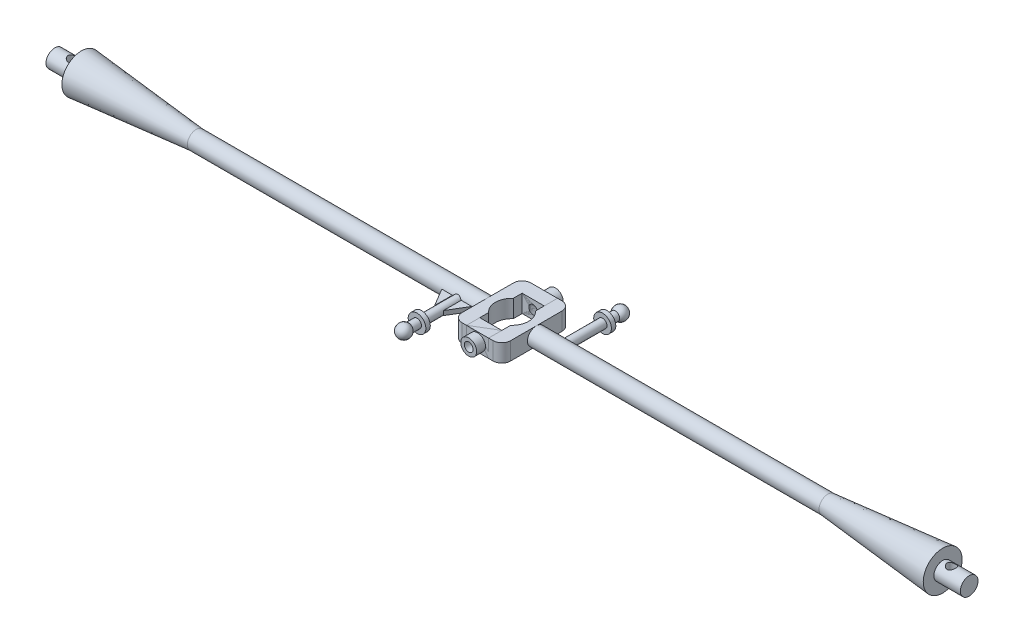
SolidWorks part; units mm, degrees
ref_plane "Front Plane" through (0, 0, 0) normal (0, 0, 1) x (1, 0, 0)
ref_plane "Top Plane" through (0, 0, 0) normal (0, 1, 0) x (1, 0, 0)
ref_plane "Right Plane" through (0, 0, 0) normal (1, 0, 0) x (0, 0, -1)
sketch "Sketch1" plane through (0, 0, 0) normal (0, 1, 0) x (1, 0, 0)
  line L0 (1.25, 3.9) -> (1.25, 2.4)
  line L1 (-1.25, 2.4) -> (1.25, 2.4)
  line L2 (-1.25, 2.4) -> (-1.25, -2.4)
  line L3 (-1.25, -2.4) -> (1.25, -2.4)
  line L4 (1.25, 2.4) -> (1.25, -2.4) construction
  line L5 (-1.25, 2.4) -> (1.25, -2.4) construction
  line L6 (-1.25, -2.4) -> (1.25, 2.4) construction
  line L7 (1.25, -3.9) -> (1.25, -2.4)
  line L9 (-2.75, -3.9) -> (1.25, -3.9)
  line L10 (-2.75, 3.9) -> (-2.75, -3.9)
  line L11 (-2.75, 3.9) -> (1.25, 3.9)
  point P0 (0, 0)
  dimension "D1" = 4.8
  dimension "D2" = 2.5
  dimension "D4" = 1.5
extrude "Boss-Extrude1" add sketch "Sketch1" along normal mid plane 2
sketch "Sketch2" plane through (0, 0, 0) normal (0, 0, 1) x (1, 0, 0)
  line L0 (-2.75, 1) -> (-2.75, -1) construction
  line L1 (-2.75, 0) -> (-35.75, 0)
  line L2 (-2.75, 0) -> (-2.75, 1)
  line L3 (-2.75, 1) -> (-35.75, 1)
  line L4 (-35.75, 0) -> (-35.75, 1) construction
  line L5 (-35.75, 1) -> (-48.75, 2.2)
  line L6 (-48.75, 2.2) -> (-48.75, 1)
  line L7 (-48.75, 1) -> (-51.75, 1)
  line L8 (-51.75, 1) -> (-51.75, 0)
  line L9 (-51.75, 0) -> (-35.75, 0)
  line L10 (-2.75, 1) -> (1.25, 1) construction
  dimension "D1" = 13
  dimension "D2" = 46
  dimension "D3" = 1
  dimension "D4" = 3
  dimension "D5" = 1.2
revolve "Revolve1" add sketch "Sketch2" angle 360 about L1
sketch "Sketch3" plane through (0, 0, 0) normal (0, 1, 0) x (1, 0, 0)
  line L0 (0, 0) -> (-10.5, 0) construction
  line L1 (-5.25, 0) -> (-5.25, -7.75)
  line L2 (-5.25, -7.75) -> (-5.25, 4.3811) construction
  line L3 (-5.25, 0) -> (-4.75, 0)
  line L4 (-4.75, 0) -> (-4.75, -5)
  line L5 (-4.75, -5) -> (-4.25, -5)
  line L6 (-4.25, -5) -> (-4.25, -5.5)
  line L7 (-4.25, -5.5) -> (-4.75, -5.5)
  line L8 (-4.75, -5.5) -> (-4.75, -6.441)
  line L9 (-2.75, 0) -> (-2.75, -3.9) construction
  arc A1 (-4.75, -6.441) -> (-5.25, -7.75) centre (-5.25, -7) cw
  dimension "D7" = 0.75
  dimension "D1" = 0.5
  dimension "D2" = 0.5
  dimension "D3" = 0.5
  dimension "D4" = 0.5
  dimension "D5" = 7.75
  dimension "D6" = 2
  dimension "D8" = 5
revolve "Revolve2" add sketch "Sketch3" angle 360 about L1
fillet "Fillet1" radius 1 2 edges at (-2.75, 0, -3.9) (-2.75, 0, 3.9)
sketch "Sketch4" plane through (0, 0, -3.9) normal (0, 0, -1) x (-1, 0, 0)
  circle A0 centre (0, 0) radius 0.9
  dimension "D1" = 1.8
extrude "Boss-Extrude2" add sketch "Sketch4" along normal mid plane 2
sketch "Sketch5" plane through (0, 0, -4.9) normal (0, 0, -1) x (-1, 0, 0)
  circle A0 centre (0, 0) radius 0.5
  dimension "D1" = 1
extrude "Cut-Extrude1" cut sketch "Sketch5" against normal through all
ref_axis "Axis1" through (0, 2.42, 0) along (0, -1, 0)
sketch "Sketch10" plane through (0, 0, 0) normal (0, 1, 0) x (1, 0, 0)
  line L0 (-6.9428, -1) -> (-5.75, -3)
  line L1 (-35.75, -1) -> (-5.75, -1) construction
  line L2 (-5.75, -1) -> (-5.75, -5) construction
  line L3 (-4.75, -3) -> (-3.5572, -1)
  line L4 (-4.75, -5) -> (-4.75, -1) construction
  line L5 (-4.75, -1) -> (-2.75, -1) construction
  line L6 (-3.5572, -1) -> (-2.75, -2.9)
  line L7 (-3.5572, 1) -> (-2.75, 2.9)
  line L8 (-2.75, 1) -> (-35.75, 1) construction
  line L9 (-2.75, 2.9) -> (-2.75, 0) construction
  line L10 (-2.75, 0) -> (-2.75, -2.9) construction
  line L11 (-2.75, -1) -> (-2.75, -2.9)
  line L12 (-2.75, 2.9) -> (-2.75, 1)
  line L13 (-2.75, 1) -> (-3.5572, 1)
  line L14 (-3.5572, -1) -> (-2.75, -1)
  line L15 (-4.75, -3) -> (-4.75, -1)
  line L16 (-5.75, -1) -> (-5.75, -3)
  line L17 (-6.9428, -1) -> (-5.75, -1)
  line L18 (-4.75, -1) -> (-3.5572, -1)
  dimension "D1" = 2.3287
extrude "Boss-Extrude16" add sketch "Sketch10" along normal mid plane 0.5 separate body contours L17 L0 L16 | L3 L15 L18 | L14 L11 L6 | L12 L13 L7 region at (-6.1476, 0, 1.6667)
sketch "Sketch12" plane through (0, 0, 0) normal (0, 1, 0) x (1, 0, 0)
  line L0 (-51.75, 1) -> (-51.75, -1) construction
  circle A0 centre (-49.75, 0) radius 0.5
  dimension "D2" = 1
  dimension "D1" = 2
extrude "Cut-Extrude2" cut sketch "Sketch12" against normal mid plane 10.5
pattern_circular "CirPattern1" count 2 over 360 about axis through (0, 2.42, 0) along (0, -1, 0) of bodies 114
sketch "Sketch13" plane through (0, 1, 0) normal (0, 1, 0) x (1, 0, 0)
  circle A0 centre (0, 0) radius 1.875
  dimension "D1" = 3.75
extrude "Cut-Extrude3" cut sketch "Sketch13" against normal blind 10
